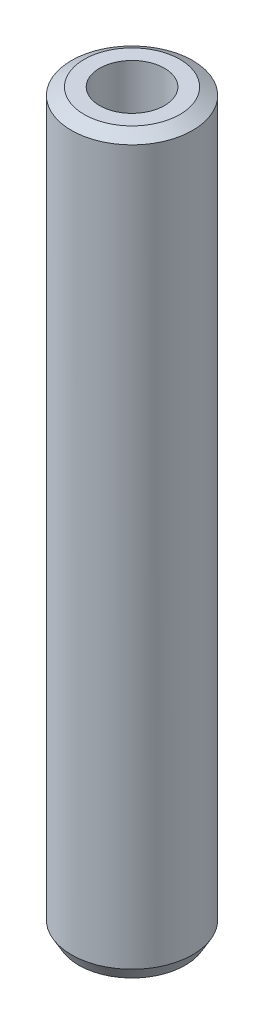
SolidWorks part; units mm, degrees
ref_plane "Front Plane" through (0, 0, 0) normal (0, 0, 1) x (1, 0, 0)
ref_plane "Top Plane" through (0, 0, 0) normal (0, 1, 0) x (1, 0, 0)
ref_plane "Right Plane" through (0, 0, 0) normal (1, 0, 0) x (0, 0, -1)
sketch "Sketch1" plane through (0, 0, 0) normal (0, 1, 0) x (1, 0, 0)
  circle A0 centre (0, 0) radius 10
  dimension "SHAFT_OD" = 20
extrude "Boss-Extrude1" add sketch "Sketch1" along normal blind 121.1309
sketch "Sketch2" plane through (0, 0, 0) normal (0, 1, 0) x (1, 0, 0)
  circle A0 centre (0, 0) radius 5.352
  dimension "BORE_D" = 10.7041
extrude "Cut-Extrude1" cut sketch "Sketch2" along normal through all
chamfer "Chamfer1" distance 1.218 angle 60 2 edges at (0, 121.1309, 10) (0, 0, 10) first distance on face at (0, 121.1309, 10) first distance on face at (0, 0, 5.352)
